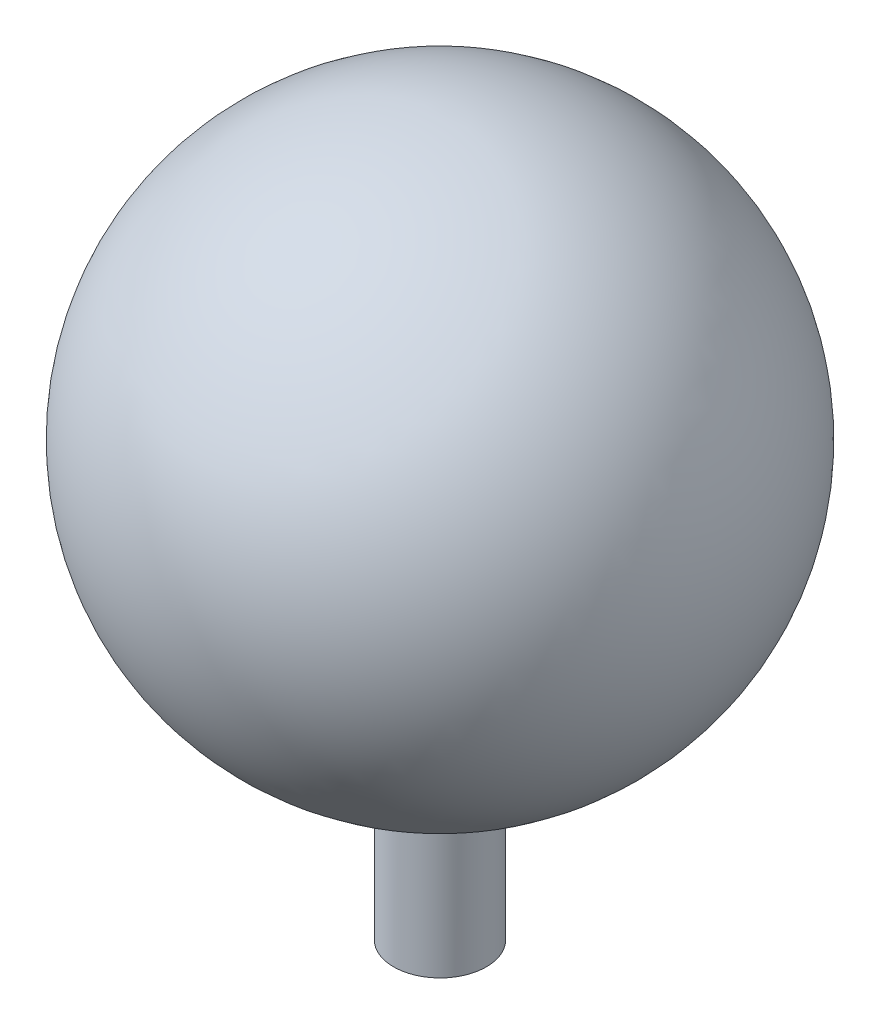
SolidWorks part; units mm, degrees
ref_plane "Front Plane" through (0, 0, 0) normal (0, 0, 1) x (1, 0, 0)
ref_plane "Top Plane" through (0, 0, 0) normal (0, 1, 0) x (1, 0, 0)
ref_plane "Right Plane" through (0, 0, 0) normal (1, 0, 0) x (0, 0, -1)
ref_axis "Axis1" through (0, -7.575, 0) along (0, 1, 0)
sketch "Sketch1" plane through (0, 0, 0) normal (0, 0, 1) x (1, 0, 0)
  line L0 (0, 4.5) -> (0, -7)
  line L1 (0, -7) -> (0.75, -7)
  line L4 (0.75, -7) -> (0.75, -4.4371)
  line L6 (0, -4.5) -> (0.75, -7) construction
  arc A0 (0.75, -4.4371) -> (0, 4.5) centre (0, 0) ccw
  point P3 (0, -4.5)
revolve "Revolve4" add sketch "Sketch1" angle 360 about L0
